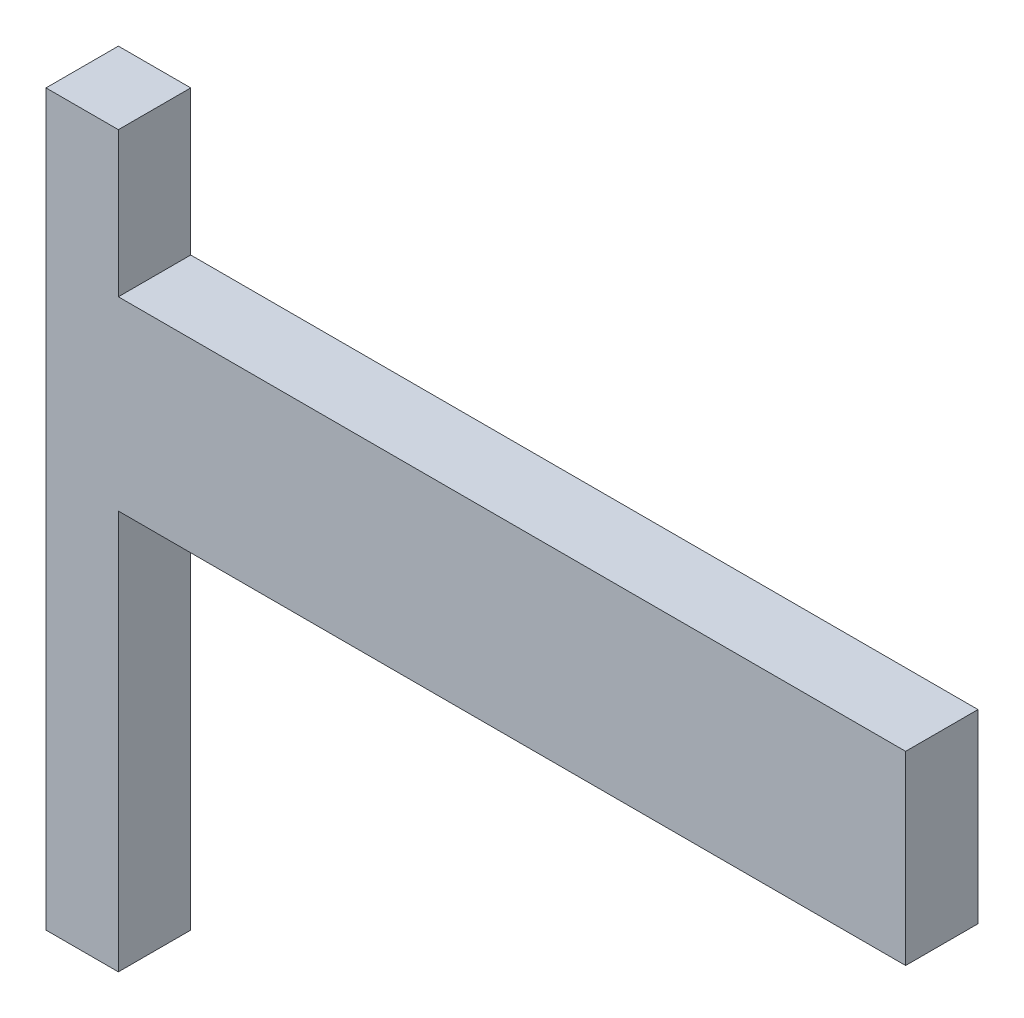
SolidWorks part; units mm, degrees
ref_plane "Front Plane" through (0, 0, 0) normal (0, 0, 1) x (1, 0, 0)
ref_plane "Top Plane" through (0, 0, 0) normal (0, 1, 0) x (1, 0, 0)
ref_plane "Right Plane" through (0, 0, 0) normal (1, 0, 0) x (0, 0, -1)
sketch "Sketch2" plane through (0, 0, 0) normal (0, 0, 1) x (1, 0, 0)
  line L0 (0, -45.0015) -> (0, 0)
  line L1 (0, 0) -> (6.35, 0)
  line L2 (6.35, 0) -> (6.35, -12.7)
  line L3 (6.35, -12.7) -> (75.4271, -12.7)
  line L4 (75.4271, -12.7) -> (75.4271, -28.978)
  line L5 (75.4271, -28.978) -> (6.35, -28.978)
  line L6 (6.35, -28.978) -> (6.35, -63.9998)
  line L7 (6.35, -63.9998) -> (0, -63.9998)
  line L8 (0, -63.9998) -> (0, -45.0015)
  dimension "D1" = 12.7
  dimension "D2" = 35.0218
  dimension "D3" = 16.278
  dimension "D4" = 6.35
  dimension "D5" = 69.0771
  dimension "D6" = 63.9998
extrude "Boss-Extrude1" add sketch "Sketch2" along normal blind 6.35
